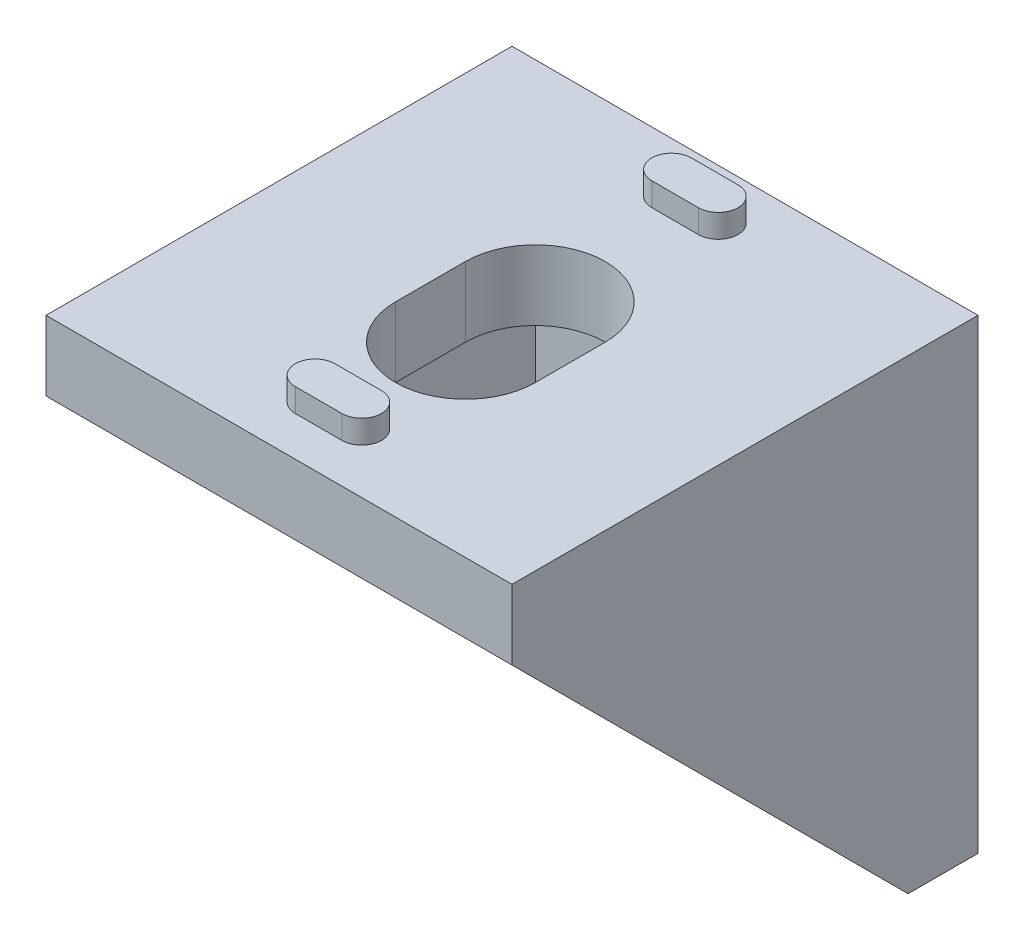
SolidWorks part; units mm, degrees
material "1060 Alloy"
ref_plane "Front Plane" through (0, 0, 0) normal (0, 0, 1) x (1, 0, 0)
ref_plane "Top Plane" through (0, 0, 0) normal (0, 1, 0) x (1, 0, 0)
ref_plane "Right Plane" through (0, 0, 0) normal (1, 0, 0) x (0, 0, -1)
sketch "Sketch1" plane through (0, 0, 0) normal (1, 0, 0) x (0, 0, -1)
  line L0 (0, 0) -> (-20, 0)
  line L1 (-20, 0) -> (-20, -3)
  line L2 (-20, -3) -> (-11.5, -11.5)
  line L3 (-11.5, -11.5) -> (0, 0) construction
  line L4 (-3, -20) -> (-11.5, -11.5)
  line L5 (0, -20) -> (-3, -20)
  line L6 (0, 0) -> (0, -20)
  dimension "D1" = 3
  dimension "D2" = 20
extrude "Boss-Extrude1" add sketch "Sketch1" along normal mid plane 20
sketch "Sketch2" plane through (0, 0, 0) normal (1, 0, 0) x (0, 0, -1)
  line L0 (-20, -3) -> (-3, -20) construction
  line L1 (-3, -3) -> (-20, -3)
  line L2 (-3, -3) -> (-3, -20)
  line L3 (-3, -20) -> (-20, -20)
  line L4 (-20, -3) -> (-20, -20)
  line L5 (-20, 0) -> (-20, -3) construction
extrude "Cut-Extrude1" cut sketch "Sketch2" against normal mid plane 12
sketch "Sketch3" plane through (0, 0, 3) normal (0, 0, 1) x (1, 0, 0)
  line L0 (0, -9) -> (0, -12) construction
  line L1 (-3, -9) -> (-3, -12)
  line L2 (3, -9) -> (3, -12)
  line L3 (0, -10.5) -> (0.7454, -10.5) construction
  line L4 (-6, -20) -> (6, -20) construction
  arc A0 (-3, -9) -> (3, -9) centre (0, -9) cw
  arc A1 (-3, -12) -> (3, -12) centre (0, -12) ccw
  dimension "D3" = 9
  dimension "D4" = 5
  dimension "D1" = 3
  dimension "D2" = 3
extrude "Cut-Extrude2" cut sketch "Sketch3" against normal up to next
sketch "Sketch4" plane through (0, 0, 0) normal (0, 0, -1) x (-1, 0, 0)
  line L0 (-1, -2.15) -> (1, -2.15) construction
  line L1 (-1, -3) -> (1, -3)
  line L2 (-1, -1.3) -> (1, -1.3)
  line L3 (0, 0) -> (0, -2.15) construction
  line L4 (-10, 0) -> (10, 0) construction
  line L5 (-2.1032, -9.8) -> (3, -9.8) construction
  line L6 (-1, -18.3) -> (1, -18.3)
  line L7 (-1, -16.6) -> (1, -16.6)
  line L8 (3, -12) -> (3, -9) construction
  arc A0 (-1, -3) -> (-1, -1.3) centre (-1, -2.15) cw
  arc A1 (1, -3) -> (1, -1.3) centre (1, -2.15) ccw
  arc A2 (1, -16.6) -> (1, -18.3) centre (1, -17.45) cw
  arc A3 (-1, -16.6) -> (-1, -18.3) centre (-1, -17.45) ccw
  dimension "D3" = 3.7
  dimension "D4" = 3
  dimension "D5" = 17
  dimension "D1" = 0.85
  dimension "D2" = 0.85
extrude "Boss-Extrude2" add sketch "Sketch4" along normal blind 1
ref_plane "Plane1" through (0, 0, 0) normal (0, 0.7071, 0.7071) x (-1, 0, 0)
mirror "Mirror1" about plane through (0, 0, 0) normal (0, 0.7071, 0.7071) of "Boss-Extrude2", "Cut-Extrude2"
